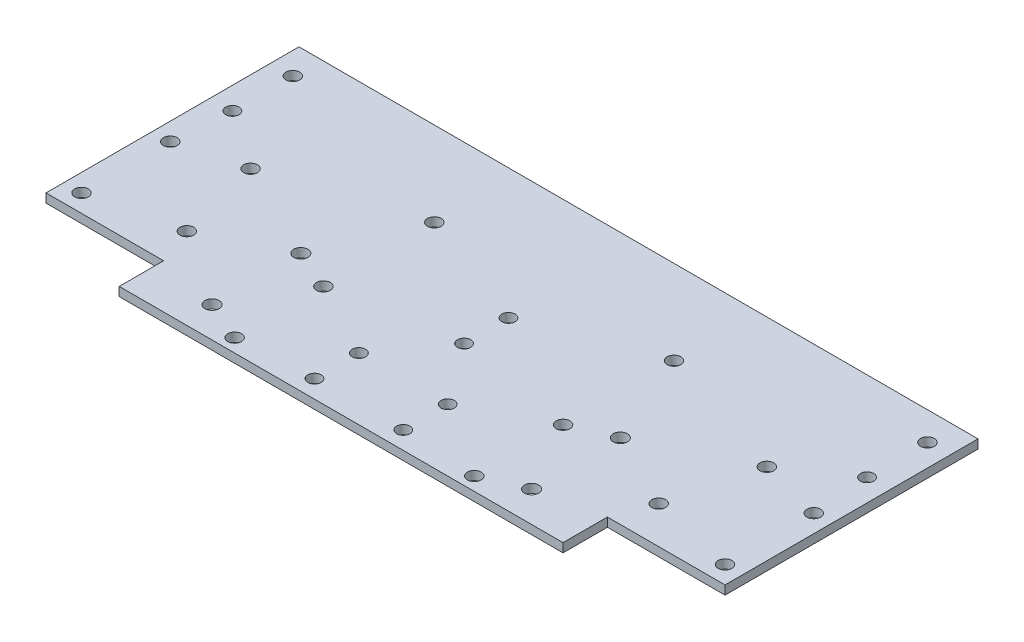
SolidWorks part; units mm, degrees
material "6061 合金"
ref_plane "前视基准面" through (0, 0, 0) normal (0, 0, 1) x (1, 0, 0)
ref_plane "上视基准面" through (0, 0, 0) normal (0, 1, 0) x (1, 0, 0)
ref_plane "右视基准面" through (0, 0, 0) normal (1, 0, 0) x (0, 0, -1)
sketch "Sketch1" plane through (0, 0, 0) normal (0, 1, 0) x (1, 0, 0)
  line L1 (-76.5, 25) -> (76.5, 25)
  line L2 (-76.5, 25) -> (-76.5, -25)
  line L3 (-76.5, -25) -> (76.5, -25)
  line L4 (76.5, 25) -> (76.5, -25)
  line L5 (-76.5, 25) -> (76.5, -25) construction
  line L6 (-76.5, -25) -> (76.5, 25) construction
  point P0 (0, 0)
  dimension "D1" = 153
  dimension "D2" = 50
extrude "Boss-Extrude1" add sketch "Sketch1" along normal blind 2
sketch "Sketch2" plane through (0, 2, 0) normal (0, 1, 0) x (1, 0, 0)
  line L0 (76.5, -25) -> (76.5, 25) construction
  line L1 (-76.5, -25) -> (76.5, -25) construction
  circle A0 centre (72.5, -21) radius 1.55
  circle A1 centre (72.5, -1) radius 1.55
  dimension "D1" = 3.1
  dimension "D2" = 3.1
  dimension "D3" = 4
  dimension "D4" = 4
  dimension "D5" = 4
  dimension "D6" = 20
extrude "Cut-Extrude1" cut sketch "Sketch2" against normal through all both and the other way through all
mirror "Mirror1" about plane through (0, 0, 0) normal (1, 0, 0) of "Cut-Extrude1"
sketch "Sketch3" plane through (0, 2, 0) normal (0, 1, 0) x (1, 0, 0)
  line L0 (-76.5, -25) -> (76.5, -25) construction
  line L1 (-30, -75) -> (30, -75)
  line L2 (-30, -75) -> (-30, 25)
  line L3 (-30, 25) -> (30, 25)
  line L4 (30, -75) -> (30, 25)
  line L5 (-30, -75) -> (30, 25) construction
  line L6 (-30, 25) -> (30, -75) construction
  line L7 (76.5, 25) -> (-76.5, 25) construction
  point P0 (0, -25)
  dimension "D1" = 60
extrude "Boss-Extrude2" add sketch "Sketch3" against normal up to surface (2 mm away) up to face at (-72.5, 0, 22.55)
sketch "Sketch4" plane through (0, 2, 0) normal (0, 1, 0) x (1, 0, 0)
  circle A0 centre (10, -21) radius 1.5
  circle A1 centre (72.5, -21) radius 1.55 construction
  circle A2 centre (-10, -21) radius 1.5
  circle A3 centre (0, 2.7) radius 1.5
  dimension "D1" = 3
  dimension "D2" = 0
  dimension "D3" = 10
  dimension "D4" = 3
  dimension "D5" = 20
  dimension "D6" = 3
  dimension "D7" = 23.7
extrude "Cut-Extrude2" cut sketch "Sketch4" against normal blind 10
sketch "Sketch5" plane through (0, 2, 0) normal (0, 1, 0) x (1, 0, 0)
  line L0 (30, -75) -> (30, -25) construction
  line L1 (-30, -75) -> (30, -75)
  line L2 (-30, -75) -> (-30, -35)
  line L3 (-30, -35) -> (30, -35)
  line L4 (30, -75) -> (30, -35)
  dimension "D1" = 40
extrude "Cut-Extrude3" cut sketch "Sketch5" against normal blind 10
sketch "Sketch6" plane through (0, 0, 0) normal (0, -1, 0) x (1, 0, 0)
  line L0 (-76.5, -25) -> (-76.5, 25) construction
  line L1 (76.5, 25) -> (76.5, -25) construction
  circle A0 centre (-71.5, -12) radius 1.5
  circle A1 centre (71.5, -12) radius 1.5
  dimension "D1" = 5
  dimension "D2" = 5
extrude "Cut-Extrude4" cut sketch "Sketch6" against normal blind 10
sketch "Sketch7" plane through (0, 2, 0) normal (0, 1, 0) x (1, 0, 0)
  line L0 (30, -35) -> (-30, -35) construction
  line L1 (-30, -25) -> (-30, -35) construction
  line L2 (30, -35) -> (30, -25) construction
  circle A0 centre (-27, -32) radius 1.55
  circle A1 centre (27, -32) radius 1.55
  dimension "D1" = 3
  dimension "D2" = 3
  dimension "D3" = 3.1
  dimension "D4" = 3.1
  dimension "D5" = 3
  dimension "D6" = 3
extrude "Cut-Extrude5" cut sketch "Sketch7" against normal blind 10
sketch "Sketch8" plane through (0, 2, 0) normal (0, 1, 0) x (1, 0, 0)
  circle A0 centre (27, 13) radius 1.55
  circle A1 centre (-27, 13) radius 1.55
  circle A2 centre (27, -12) radius 1.55
  circle A3 centre (-27, -12) radius 1.55
  circle A4 centre (-27, -32) radius 1.55 construction
  circle A5 centre (27, -32) radius 1.55 construction
  dimension "D1" = 3.1
  dimension "D2" = 3.1
  dimension "D3" = 3.1
  dimension "D4" = 3.1
  dimension "D5" = 0
  dimension "D6" = 20
  dimension "D7" = 0
  dimension "D8" = 20
  dimension "D9" = 0
  dimension "D10" = 0
  dimension "D11" = 25
  dimension "D12" = 25
extrude "Cut-Extrude6" cut sketch "Sketch8" against normal blind 10
sketch "Sketch9" plane through (0, 2, 0) normal (0, 1, 0) x (1, 0, 0)
  circle A0 centre (-10, -31) radius 1.5
  circle A1 centre (10, -31) radius 1.5
  circle A2 centre (0, -7.3) radius 1.5
  circle A3 centre (-10, -21) radius 1.5 construction
  circle A4 centre (10, -21) radius 1.5 construction
  circle A5 centre (0, 2.7) radius 1.5 construction
  dimension "D1" = 3
  dimension "D2" = 3
  dimension "D3" = 3
  dimension "D4" = 10
  dimension "D5" = 10
  dimension "D6" = 10
extrude "Cut-Extrude7" cut sketch "Sketch9" against normal blind 35
sketch "Sketch10" plane through (0, 2, 0) normal (0, 1, 0) x (1, 0, 0)
  line L0 (0, -35) -> (0, 25) construction
  line L1 (30, -35) -> (-30, -35) construction
  line L2 (76.5, 25) -> (-76.5, 25) construction
  circle A0 centre (58.1669, 2.757) radius 1.55
  circle A1 centre (53.1561, -16.6052) radius 1.55
  circle A2 centre (-53.1561, -16.6052) radius 1.55
  circle A3 centre (-58.1669, 2.757) radius 1.55
extrude "Cut-Extrude8" cut sketch "Sketch10" against normal blind 10
sketch "Sketch11" plane through (0, 0, 0) normal (0, -1, 0) x (1, 0, 0)
  line L0 (76.5, 25) -> (76.5, -25) construction
  line L1 (-76.5, -25) -> (76.5, -25)
  line L2 (-76.5, -25) -> (-76.5, -17)
  line L3 (-76.5, -17) -> (76.5, -17)
  line L4 (76.5, -25) -> (76.5, -17)
  circle A0 centre (71.5, -12) radius 1.5 construction
  dimension "D1" = 5
extrude "Cut-Extrude9" cut sketch "Sketch11" against normal blind 10
sketch "Sketch12" plane through (0, 0, 0) normal (0, -1, 0) x (1, 0, 0)
  line L0 (30, 25) -> (76.5, 25) construction
  line L1 (30, 35) -> (50, 35)
  line L2 (30, 35) -> (30, 25)
  line L3 (30, 25) -> (50, 25)
  line L4 (50, 35) -> (50, 25)
  line L5 (-76.5, 25) -> (-30, 25) construction
  line L6 (-30, 35) -> (-50, 35)
  line L7 (-30, 35) -> (-30, 25)
  line L8 (-30, 25) -> (-50, 25)
  line L9 (-50, 35) -> (-50, 25)
  dimension "D1" = 20
  dimension "D2" = 20
extrude "Boss-Extrude3" add sketch "Sketch12" against normal up to surface (2 mm away) up to face at (0, 2, 17)
sketch "Sketch13" plane through (0, 0, 0) normal (0, -1, 0) x (1, 0, 0)
  circle A2 centre (-36, 28.0912) radius 1.6
  circle A3 centre (-36, 8.0912) radius 1.6
  circle A4 centre (36, 28.0912) radius 1.6
  circle A5 centre (36, 8.0912) radius 1.6
extrude "Cut-Extrude10" cut sketch "Sketch13" against normal blind 10
sketch "Sketch14" plane through (0, 2, 0) normal (0, 1, 0) x (1, 0, 0)
  line L1 (-76.5, 17) -> (76.5, 17)
  line L2 (-76.5, 17) -> (-76.5, 32)
  line L3 (-76.5, 32) -> (76.5, 32)
  line L4 (76.5, 17) -> (76.5, 32)
  dimension "D1" = 15
extrude "Boss-Extrude4" add sketch "Sketch14" against normal up to surface (2 mm away) up to face at (-36, 0, 6.4912)
sketch "Sketch15" plane through (0, 0, 0) normal (0, -1, 0) x (1, 0, 0)
  circle A0 centre (71.5, -25.6088) radius 1.55
  circle A1 centre (-71.5, -25.6088) radius 1.55
extrude "Cut-Extrude11" cut sketch "Sketch15" against normal blind 10
